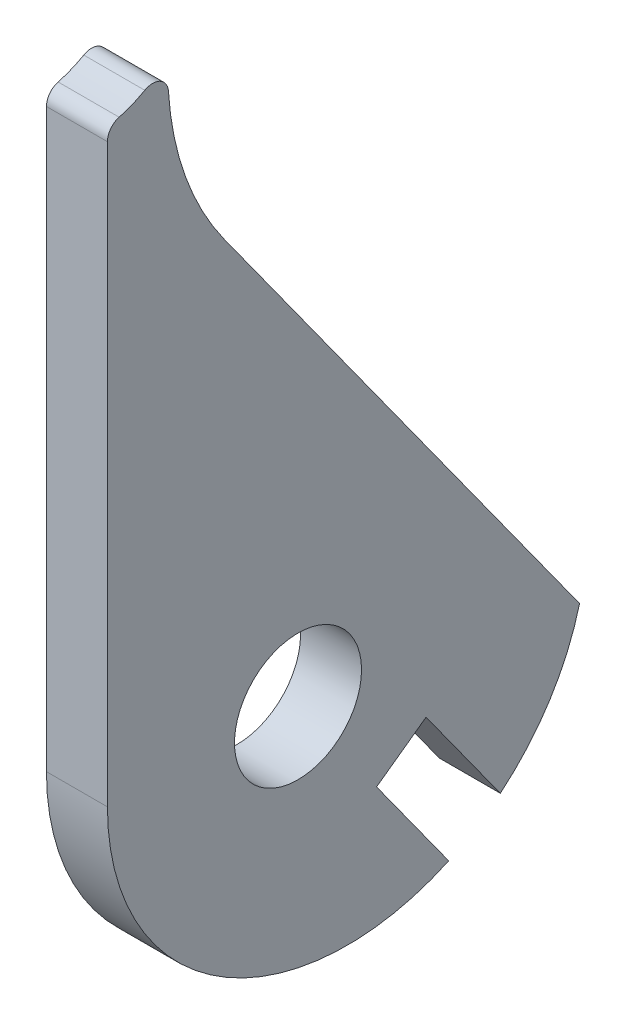
SolidWorks part; units mm, degrees
ref_plane "Front Plane" through (0, 0, 0) normal (0, 0, 1) x (1, 0, 0)
ref_plane "Top Plane" through (0, 0, 0) normal (0, 1, 0) x (1, 0, 0)
ref_plane "Right Plane" through (0, 0, 0) normal (1, 0, 0) x (0, 0, -1)
sketch "Sketch1" plane through (0, 0, 0) normal (1, 0, 0) x (0, 0, -1)
  line L0 (-9.525, 29.2032) -> (-9.525, 0.4134)
  line L3 (14.0715, -2.5834) -> (-3.6904, 22.0658)
  arc A0 (-8.938, 29.9695) -> (-7.6582, 30.4948) centre (-10.372, 35.2842) ccw
  arc A1 (-6.4747, 29.8537) -> (-3.6904, 22.0658) centre (8.4053, 30.7818) ccw
  arc A2 (-9.525, 0.4134) -> (14.0715, -2.5834) centre (2.4635, 0.4134) ccw
  arc A3 (-6.4747, 29.8537) -> (-7.6582, 30.4948) centre (-7.2669, 29.8042) ccw
  arc A4 (-9.525, 29.2032) -> (-8.938, 29.9695) centre (-8.7312, 29.2032) cw
  point P13 (-9.525, 29.845)
  dimension "D4" = 0.7937
  dimension "D1" = 9.525
  dimension "D2" = 9.906
  dimension "D3" = 29.845
  dimension "D5" = 35.776
extrude "Boss-Extrude1" add sketch "Sketch1" along normal mid plane 3.048
sketch "Sketch2" plane through (1.524, 0, 0) normal (1, 0, 0) x (0, 0, -1)
  circle A0 centre (0, 0) radius 3.175
  dimension "D1" = 6.35
extrude "Cut-Extrude1" cut sketch "Sketch2" against normal through all
ref_axis "Axis1" through (-1.7463, 0, 0) along (1, 0, 0)
sketch "Sketch3" plane through (1.524, 0, 0) normal (1, 0, 0) x (0, 0, -1)
  line L0 (3.9264, -5.4489) -> (7.5312, -10.4514)
  line L1 (6.3993, -3.667) -> (10.1116, -8.8188)
  line L2 (6.3993, -3.667) -> (3.9264, -5.4489)
  line L3 (14.0715, -2.5834) -> (-3.6904, 22.0658) construction
  line L4 (6.3993, -3.667) -> (11.9771, -11.4076) construction
  line L5 (3.9264, -5.4489) -> (9.5042, -13.1895) construction
  line L6 (11.4279, -15.8591) -> (0, 0) construction
  arc A0 (-9.525, 0.4134) -> (14.0715, -2.5834) centre (2.4635, 0.4134) ccw construction
  arc A1 (7.5312, -10.4514) -> (10.1116, -8.8188) centre (2.4635, 0.4134) ccw
  dimension "D3" = 6.35
  dimension "D1" = 3.048
extrude "Cut-Extrude2" cut sketch "Sketch3" against normal through all
